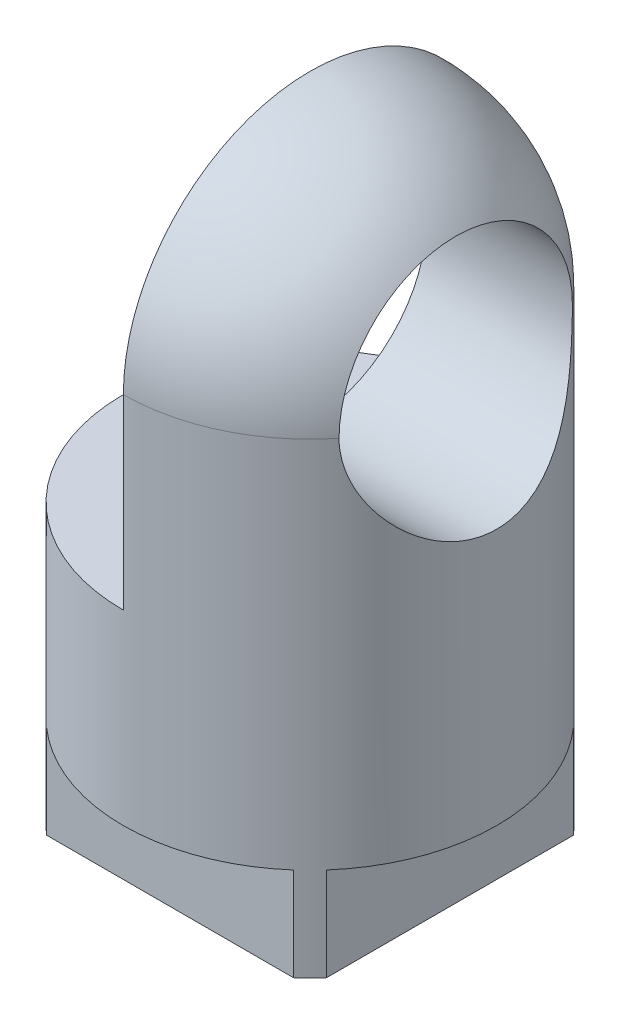
SolidWorks part; units mm, degrees
ref_plane "Front Plane" through (0, 0, 0) normal (0, 0, 1) x (1, 0, 0)
ref_plane "Top Plane" through (0, 0, 0) normal (0, 1, 0) x (1, 0, 0)
ref_plane "Right Plane" through (0, 0, 0) normal (1, 0, 0) x (0, 0, -1)
sketch "Sketch1" plane through (0, 0, 0) normal (0, 0, 1) x (1, 0, 0)
  line L0 (-5.08, 0) -> (-5.08, 12.7)
  line L2 (-5.08, 0) -> (0, 0)
  line L3 (0, 17.78) -> (0, 12.7)
  line L4 (0, 0) -> (5.08, 0) construction
  line L5 (0, 12.7) -> (-5.08, 12.7) construction
  line L6 (0, 12.7) -> (0, 7.62)
  line L7 (0, 7.62) -> (0, 0)
  line L8 (0, 7.62) -> (-5.08, 7.62)
  arc A0 (0, 17.78) -> (-5.08, 12.7) centre (0, 12.7) ccw
  dimension "D1" = 10.16
  dimension "D2" = 7.62
revolve "Revolve1" add sketch "Sketch1" angle 360 about L6 region at (-2.54, 3.81, 0) region at (-2.3711, 12.2258, 0)
extrude "Cut-Extrude1" cut sketch "Sketch1<3>" against normal through all both and the other way through all contours L3 A0 L0 L8 L6 region at (-2.3711, 12.2258, 0)
sketch "Sketch1<3>" plane through (0, 0, 0) normal (0, 0, 1) x (1, 0, 0) same geometry as "Sketch1"
sketch "Sketch2" plane through (0, 0, 0) normal (0, -1, 0) x (1, 0, 0)
  circle A0 centre (0, 0) radius 3.175
  dimension "D1" = 6.35
extrude "Cut-Extrude2" cut sketch "Sketch2" against normal blind 6.35
sketch "Sketch3" plane through (0, 0, 0) normal (-1, 0, 0) x (0, 0, 1)
  arc A0 (5.08, 12.7) -> (-5.08, 12.7) centre (0, 12.7) ccw construction
  arc A1 (5.08, 12.7) -> (-5.08, 12.7) centre (0, 12.7) ccw construction
  circle A2 centre (0, 12.7) radius 3.175
  dimension "D1" = 6.35
extrude "Cut-Extrude3" cut sketch "Sketch3" against normal through all
sketch "Sketch4" plane through (0, 0, 0) normal (0, 1, 0) x (1, 0, 0)
  line L1 (-3.81, -3.81) -> (3.81, -3.81)
  line L2 (-3.81, -3.81) -> (-3.81, 3.81)
  line L3 (-3.81, 3.81) -> (3.81, 3.81)
  line L4 (3.81, -3.81) -> (3.81, 3.81)
  line L5 (-3.81, -3.81) -> (3.81, 3.81) construction
  line L6 (-3.81, 3.81) -> (3.81, -3.81) construction
  circle A0 centre (0, 0) radius 13.0639
  point P0 (0, 0)
  dimension "D1" = 7.62
extrude "Cut-Extrude4" cut sketch "Sketch4" along normal blind 2.54 contours A0 L4 L1 L2 L3 region at (-12.6944, 0, 0)
